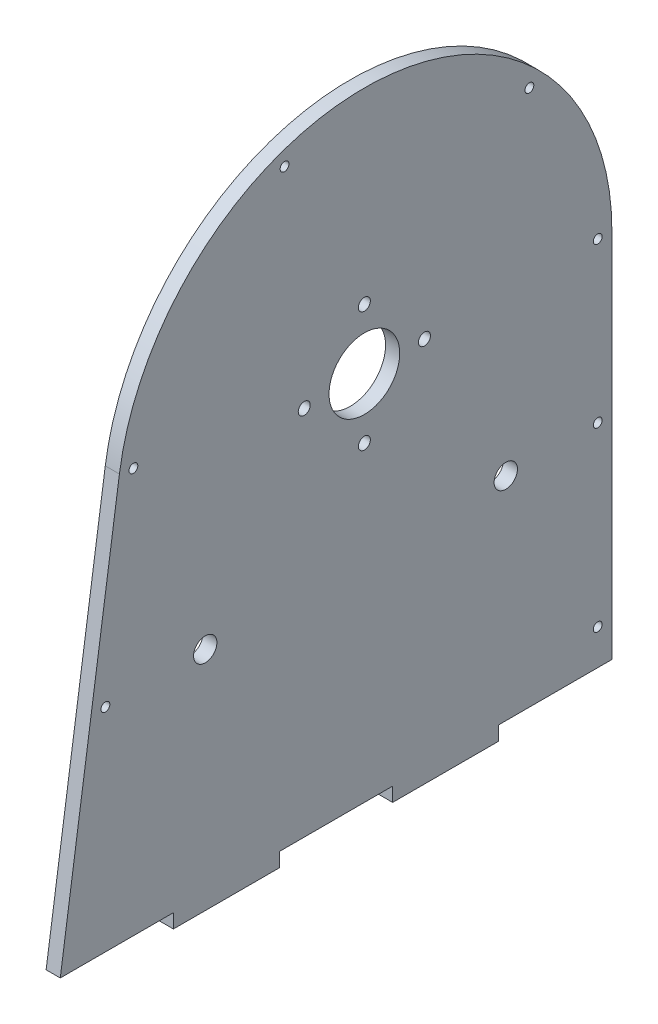
SolidWorks part; units mm, degrees
ref_plane "Ebene vorne" through (0, 0, 0) normal (1, 0, 0) x (0, 1, 0)
ref_plane "Ebene oben" through (0, 0, 0) normal (0, 0, 1) x (0, 1, 0)
ref_plane "Ebene rechts" through (0, 0, 0) normal (0, 1, 0) x (-1, 0, 0)
sketch "Skizze1" plane through (0, 0, 0) normal (1, 0, 0) x (0, 0, -1)
  line L0 (-80.9035, -101.1719) -> (-80.9035, -97.0207)
  line L1 (-121.1235, -18.7355) -> (-120.9035, -18.7355) construction
  line L2 (-96.4035, -81.5207) -> (-102.1906, -81.5207)
  line L3 (-80.9035, -63.7029) -> (-80.9035, -66.0207)
  line L4 (-80.9035, -101.1719) -> (-80.9035, -97.0207)
  line L5 (-61.4088, -81.5207) -> (-65.4035, -81.5207)
  line L6 (-80.9035, -66.0207) -> (-80.9035, -63.7029)
  line L7 (-120.9035, -13.3959) -> (-120.9035, -24.0751)
  line L39 (-10.9035, -186.5207) -> (-166.9035, -186.5207)
  line L40 (-166.9035, -186.5207) -> (-150.1753, -71.4505)
  line L41 (-61.4088, -81.5207) -> (-65.4035, -81.5207)
  line L42 (-10.9035, -81.5207) -> (-10.9035, -186.5207)
  line L43 (-166.9035, -186.5207) -> (-121.9035, -186.5207)
  line L47 (-10.9035, -186.5207) -> (-81.9035, -186.5207)
  line L52 (-1.9035, -186.5207) -> (-10.9035, -186.5207)
  line L54 (-1.9035, -81.5207) -> (-1.9035, -186.5207)
  circle A1 centre (-80.9035, -81.5207) radius 10
  circle A2 centre (-80.9035, -81.5207) radius 15.5
  arc A3 (-38.3408, -137.0943) -> (-38.2029, -136.9884) centre (-80.9035, -81.5207) ccw
  arc A4 (-112.4679, -144.0002) -> (-112.3746, -144.0473) centre (-80.9035, -81.5207) ccw
  arc A6 (-10.9035, -81.5207) -> (-150.1753, -71.4505) centre (-80.9035, -81.5207) ccw
  arc A9 (-38.3408, -137.0943) -> (-38.2029, -136.9884) centre (-80.9035, -81.5207) ccw
  arc A10 (-120.9035, -24.0751) -> (-150.1753, -71.4505) centre (-80.9035, -81.5207) ccw
  arc A11 (-112.4679, -144.0002) -> (-112.3746, -144.0473) centre (-80.9035, -81.5207) ccw
  circle A12 centre (-27.828, -81.5207) radius 3
  circle A13 centre (-44.9035, -120.5207) radius 3
  circle A14 centre (-44.9035, -42.5207) radius 3
  circle A15 centre (-116.9035, -42.5207) radius 3
  circle A16 centre (-116.9035, -120.5207) radius 3
  arc A18 (-1.9035, -81.5207) -> (-120.9035, -13.3959) centre (-80.9035, -81.5207) ccw
  circle A19 centre (-133.9789, -81.5207) radius 3
  circle A20 centre (-80.9035, -28.4453) radius 3
  circle A21 centre (-80.9035, -134.5962) radius 3
  circle A23 centre (-80.9035, -46.5207) radius 1
  circle A24 centre (-80.9035, -116.5207) radius 1
  point P19 (-120.9035, -18.7355)
  point P91 (-121.1235, -18.7355)
  dimension "D1" = 156
  dimension "D2" = 70
extrude "Aufsatz-Linear austragen1" add sketch "Skizze1" along normal blind 4 contours L39 L40 A10 L7 A18 L54 L52
extrude "Schnitt-Linear austragen1" cut sketch "Skizze1<9>" along normal blind 6 contours A1
sketch "Skizze1<9>" plane through (0, 0, 0) normal (1, 0, 0) x (0, 0, -1) same geometry as "Skizze1"
hole_wizard "Durchgangsloch für M31" positions "Skizze2" profile "Skizze3" hole size "M3" standard "DIN"
sketch "Skizze2" plane through (0, 0, 0) normal (-1, 0, 0) x (0, 0, 1)
  line L0 (80.9035, -81.5207) -> (63.9035, -81.5207) construction
  circle A1 centre (80.9035, -81.5207) radius 10 construction
  point P15 (63.9035, -81.5207)
  dimension "D1" = 17
sketch "Skizze3" plane through (0, -81.5207, 63.9035) normal (0, 1, 0) x (0, 0, 1)
  line L0 (0, 0) -> (0, 21.0215)
  line L1 (0, 21.0215) -> (1.7, 20)
  line L2 (1.7, 20) -> (1.7, 0)
  line L5 (1.7, 0) -> (0, 0)
  line L10 (0, 21.0215) -> (-1.7, 20) construction
  line L11 (0, -6.35) -> (0, 107.95) construction
  dimension "Bohrerdurchmesser" = 3.4
  dimension "Bohrungstiefe" = 20
  dimension "Spitzenwinkel" = 118
sketch "Skizze4" plane through (0, 0, 0) normal (1, 0, 0) x (0, 0, -1)
  line L0 (-10.9035, -81.5207) -> (-151.4737, -81.5207)
  line L1 (-146.9035, -81.5207) -> (-159.5903, -180.7127)
  line L2 (-80.9035, -11.5207) -> (-80.9035, -186.5207)
  line L3 (-14.9035, -81.5207) -> (-14.9035, -131.5207)
  line L4 (-80.9035, -11.5207) -> (-80.9035, -81.5207)
  line L5 (-102.9035, -81.5207) -> (-113.4035, -81.5207)
  line L6 (-80.9035, -59.5207) -> (-80.9035, -49.0207)
  line L7 (-58.9035, -81.5207) -> (-48.4035, -81.5207)
  line L8 (-80.9035, -103.5207) -> (-80.9035, -114.0207)
  line L9 (-80.9035, -11.5207) -> (-80.9035, -15.5207)
  line L10 (-10.9035, -81.5207) -> (-14.9035, -81.5207)
  line L11 (-151.4737, -81.5207) -> (-146.9035, -81.5207)
  line L12 (-14.9035, -131.5207) -> (-14.9035, -181.5207)
  line L14 (-80.9035, -81.5207) -> (-129.4035, -81.5207)
  line L15 (-25.9035, -171.5208) -> (-55.9035, -171.5208)
  line L16 (-131.2851, -110.731) -> (-126.3188, -110.731)
  line L17 (-35.9035, -118.0036) -> (-42.9648, -118.0036)
  line L18 (-95.9035, -145.7936) -> (-95.9035, -136.0643)
  line L19 (-65.9035, -145.7936) -> (-65.9035, -136.0643)
  line L20 (-147.8627, -186.5207) -> (-147.8627, -171.5208)
  line L21 (-80.9035, -81.5207) -> (-80.9035, -36.7507)
  line L24 (-141.2043, -119.4623) -> (-147.8627, -171.5208)
  line L25 (-147.8627, -171.5208) -> (-135.9031, -171.5208)
  line L26 (-80.9035, -81.5207) -> (-32.4035, -81.5207)
  line L27 (-25.9035, -128.0036) -> (-25.9035, -171.5208)
  line L29 (-80.9035, -181.5207) -> (-80.9035, -139.7707)
  line L31 (-65.9035, -161.5208) -> (-65.9035, -145.7936)
  line L33 (-80.9035, -181.5207) -> (-80.9035, -136.3407)
  line L35 (-95.9035, -161.5208) -> (-95.9035, -145.7936)
  line L36 (-105.9035, -171.5208) -> (-135.9031, -171.5208)
  line L37 (-80.9035, -81.5207) -> (-80.9035, -36.7507)
  line L40 (-80.9035, -81.5207) -> (-36.1335, -81.5207)
  line L41 (-80.9035, -81.5207) -> (-80.9035, -33.0207)
  line L44 (-80.9035, -81.5207) -> (-125.6735, -81.5207)
  line L45 (-80.9035, -81.5207) -> (-80.9035, -33.0207)
  circle A1 centre (-80.9035, -81.5207) radius 22
  circle A2 centre (-80.9035, -81.5207) radius 27
  circle A4 centre (-146.9035, -81.5207) radius 1.2501
  circle A5 centre (-14.9035, -81.5207) radius 1.2501
  circle A6 centre (-80.9035, -15.5207) radius 1.25
  circle A7 centre (-48.4035, -81.5207) radius 1.65
  arc A10 (-14.9107, -82.7708) -> (-146.8962, -82.7708) centre (-80.9035, -81.5207) ccw
  arc A11 (-118.7496, -114.196) -> (-101.7368, -126.9737) centre (-80.9035, -81.5207) ccw
  arc A12 (-60.0701, -126.9737) -> (-49.2879, -120.2565) centre (-80.9035, -81.5207) ccw
  arc A13 (-25.9035, -128.0036) -> (-35.9035, -118.0036) centre (-35.9035, -128.0036) ccw
  arc A14 (-49.2879, -120.2565) -> (-42.9648, -118.0036) centre (-42.9648, -128.0036) cw
  arc A15 (-65.9035, -136.0643) -> (-60.0701, -126.9737) centre (-55.9035, -136.0643) cw
  arc A16 (-95.9035, -136.0643) -> (-101.7368, -126.9737) centre (-105.9035, -136.0643) ccw
  arc A17 (-126.3188, -110.731) -> (-118.7496, -114.196) centre (-126.3188, -120.731) cw
  arc A18 (-141.2043, -119.4623) -> (-131.2851, -110.731) centre (-131.2851, -120.731) cw
  arc A19 (-55.9035, -171.5208) -> (-65.9035, -161.5208) centre (-55.9035, -161.5208) cw
  arc A20 (-105.9035, -171.5208) -> (-95.9035, -161.5208) centre (-105.9035, -161.5208) ccw
  circle A22 centre (-125.6735, -33.0207) radius 1.5
  circle A23 centre (-36.1335, -33.0207) radius 1.5
  point P67 (-65.9035, -129.2177)
  dimension "D3" = 10
  dimension "D4" = 10
extrude "Schnitt-Linear austragen2" cut sketch "Skizze1<18>" against normal blind 10 and the other way through all contours L54 A18 L7 A6 L42 L52 region at (0, -14.8623, 42.7429)
sketch "Skizze1<18>" plane through (0, 0, 0) normal (1, 0, 0) x (0, 0, -1) same geometry as "Skizze1"
sketch "Skizze21" plane through (4, 0, 0) normal (1, 0, 0) x (0, 1, 0)
  circle A0 centre (-81.5207, 80.9035) radius 37.5 construction
  dimension "D1" = 75
sketch "Skizze27" plane through (4, 0, 0) normal (1, 0, 0) x (0, 1, 0)
  line L2 (-186.5207, 10.9035) -> (-186.5207, 166.9035) construction
  line L3 (-81.5207, 14.9035) -> (-186.5207, 14.9035)
  line L4 (-81.5207, 14.9035) -> (-186.5207, 14.9035) construction
  line L5 (-34.8517, 34.2344) -> (-81.5207, 80.9035) construction
  line L6 (-81.5207, 80.9035) -> (-81.5207, 14.9035) construction
  line L7 (-81.5207, 80.9035) -> (-19.501, 103.4768) construction
  line L11 (-186.5207, 166.9035) -> (-71.4505, 150.1753) construction
  arc A2 (-81.5207, 14.9035) -> (-72.0259, 146.2169) centre (-81.5207, 80.9035) ccw
  arc A3 (-81.5207, 14.9035) -> (-72.0259, 146.2169) centre (-81.5207, 80.9035) ccw construction
  point P0 (-176.5207, 14.9035)
  point P1 (-126.5207, 14.9035)
  point P4 (-34.8517, 34.2344)
  point P5 (-34.8517, 34.2344)
  point P8 (-19.501, 103.4768)
  point P11 (-81.5207, 14.9035)
  point P12 (-72.0259, 146.2169)
  point P17 (-176.5207, 14.9035)
  point P19 (-126.5207, 14.9035)
  point P41 (-126.5207, 154.139)
  dimension "D2" = 10
  dimension "D3" = 60
  dimension "D4" = 45
  dimension "D5" = 110
  dimension "D6" = 60
  dimension "D7" = 4
  dimension "D1" = 4
hole_wizard "M3 Gewindebohrung1" positions "Skizze27" profile "Skizze28" tap size "M3" standard "DIN"
sketch "Skizze28" plane through (4, -176.5207, 14.9035) normal (0, 1, 0) x (0, 0, -1)
  line L0 (0, 0) -> (0, 9.2511)
  line L1 (0, 9.2511) -> (1.25, 8.5)
  line L2 (1.25, 8.5) -> (1.25, 0)
  line L5 (1.25, 0) -> (0, 0)
  line L10 (0, 9.2511) -> (-1.25, 8.5) construction
  line L11 (0, -6.35) -> (0, 107.95) construction
  dimension "Bohrerdurchmesser" = 2.5
  dimension "Bohrungstiefe" = 8.5
  dimension "Spitzenwinkel" = 118
pattern_circular "Kreismuster1" count 4 over 360 about axis through (0, -81.5207, 80.9035) along (1, 0, 0) of "Durchgangsloch für M31"
hole_wizard "Durchgangsloch für M61" positions "Skizze29" profile "Skizze31" hole size "M6" standard "DIN"
sketch "Skizze29" plane through (0, 0, 0) normal (-1, 0, 0) x (0, 0, 1)
  line L0 (10.9035, -186.5207) -> (166.9035, -186.5207) construction
  line L8 (10.9035, -186.5207) -> (10.9035, -81.5207) construction
  point P0 (40.9035, -126.5207)
  point P2 (125.9035, -126.5207)
  dimension "D1" = 60
  dimension "D2" = 60
  dimension "D5" = 30
  dimension "D6" = 85
sketch "Skizze31" plane through (0, -126.5207, 40.9035) normal (0, 1, 0) x (0, 0, 1)
  line L0 (0, 0) -> (0, 18.9828)
  line L1 (0, 18.9828) -> (3.3, 17)
  line L2 (3.3, 17) -> (3.3, 0)
  line L5 (3.3, 0) -> (0, 0)
  line L10 (0, 18.9828) -> (-3.3, 17) construction
  line L11 (0, -6.35) -> (0, 107.95) construction
  dimension "Bohrerdurchmesser" = 6.6
  dimension "Bohrungstiefe" = 17
  dimension "Spitzenwinkel" = 118
sketch "Skizze32" plane through (0, -186.5207, 0) normal (0, -1, 0) x (1, 0, 0)
  line L0 (0, 10.9035) -> (0, 166.9035) construction
  line L1 (0, 134.9035) -> (4, 134.9035)
  line L2 (0, 134.9035) -> (0, 104.9035)
  line L3 (0, 104.9035) -> (4, 104.9035)
  line L4 (4, 134.9035) -> (4, 104.9035)
  line L5 (4, 10.9035) -> (4, 166.9035) construction
  line L6 (4, 166.9035) -> (0, 166.9035) construction
  line L7 (4, 43.4035) -> (4, 118.4035) construction
  line L8 (0, 42.9035) -> (4, 42.9035)
  line L9 (0, 42.9035) -> (0, 72.9035)
  line L10 (0, 72.9035) -> (4, 72.9035)
  line L11 (4, 42.9035) -> (4, 72.9035)
  line L12 (4, 10.9035) -> (0, 10.9035) construction
  dimension "D1" = 30
  dimension "D2" = 32
  dimension "D3" = 30
  dimension "D4" = 32
extrude "Aufsatz-Linear austragen2" add sketch "Skizze32" along normal blind 4
equation "\"D2@Skizze29\"=\"D1@Skizze29\""
equation "\"D4@Skizze32\"=\"D2@Skizze32\""
